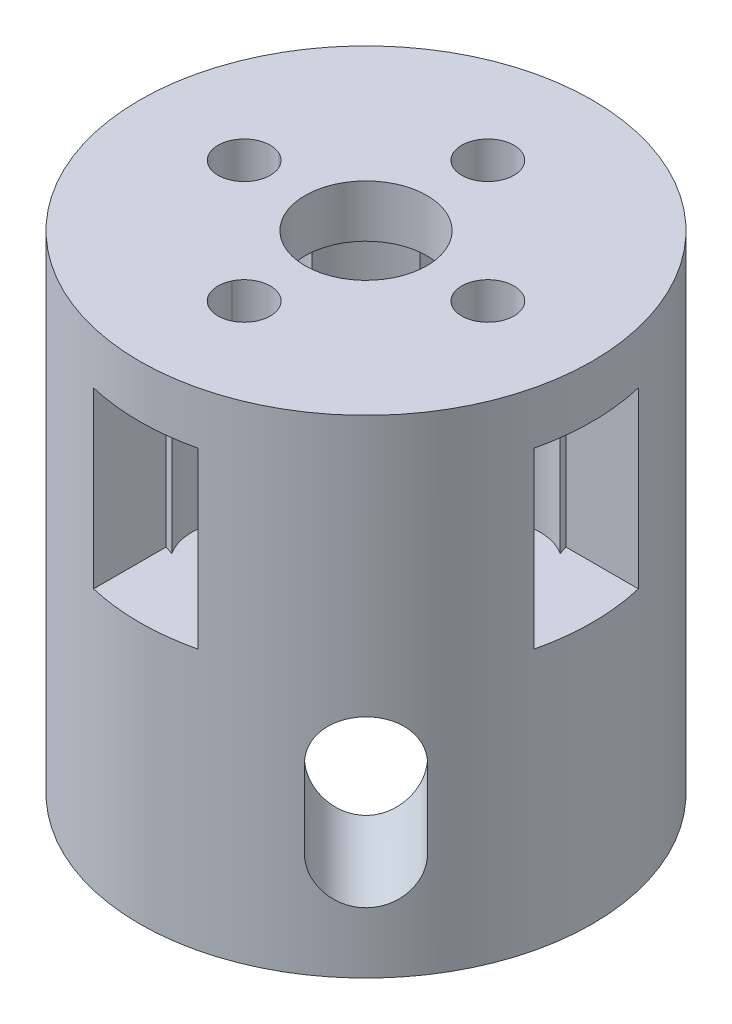
SolidWorks part; units mm, degrees
note: The reader was unsure of these and kept them because the rebuilt part matched: shared geometry of "Sketch1<4>", "Sketch1<7>", "Sketch1<6>".
ref_plane "Front Plane" through (0, 0, 0) normal (0, 0, 1) x (1, 0, 0)
ref_plane "Top Plane" through (0, 0, 0) normal (0, 1, 0) x (1, 0, 0)
ref_plane "Right Plane" through (0, 0, 0) normal (1, 0, 0) x (0, 0, -1)
sketch "Sketch1" plane through (0, 0, 0) normal (0, 1, 0) x (1, 0, 0)
  line L0 (-7, 0) -> (7, 0) construction
  circle A0 centre (0, 0) radius 13
  circle A1 centre (0, 0) radius 6.5
  circle A2 centre (0, 0) radius 9
  circle A3 centre (-7, 0) radius 1.5
  circle A4 centre (7, 0) radius 1.5
  circle A5 centre (0, 7) radius 1.5
  circle A6 centre (0, -7) radius 1.5
  circle A7 centre (7, 0) radius 3
  circle A8 centre (0, -7) radius 3
  circle A9 centre (-7, 0) radius 3
  circle A10 centre (0, 7) radius 3
  circle A11 centre (0, 0) radius 3.5
  point P16 (0, 0)
  point P24 (0, 0)
  dimension "D1" = 26
  dimension "D2" = 13
  dimension "D3" = 18
  dimension "D4" = 3
  dimension "D5" = 3
  dimension "D9" = 6
  dimension "D11" = 7
  dimension "D6" = 14
  dimension "D8" = 7
  dimension "D7" = 2
  dimension "D10" = 4
extrude "Boss-Extrude2" add sketch "Sketch1" against normal blind 25 contours A9 A2 A8 A1 | A8 A2 A7 A1 | A10 A1 A7 A2 | A10 A2 A9 A1
extrude "Boss-Extrude3" add sketch "Sketch1<4>" along normal blind 3
sketch "Sketch1<4>" plane through (0, 0, 0) normal (0, 1, 0) x (1, 0, 0) same geometry as "Sketch1"
extrude "Cut-Extrude2" cut sketch "Sketch1<7>" along normal up to surface (3 mm away) contours A1 A5
sketch "Sketch1<7>" plane through (0, 0, 0) normal (0, 1, 0) x (1, 0, 0) same geometry as "Sketch1"
extrude "Boss-Extrude4" add sketch "Sketch1<6>" against normal blind 15 from offset 10 offset against normal yes
sketch "Sketch1<6>" plane through (0, 0, 0) normal (0, 1, 0) x (1, 0, 0) same geometry as "Sketch1"
ref_plane "Plane1" through (6.364, 0, 6.364) normal (0.7071, 0, 0.7071) x (0.7071, 0, -0.7071)
sketch "Sketch3" plane through (0, 0, 0) normal (0, -1, 0) x (1, 0, 0)
  line L0 (-3, 12.6491) -> (-3, -12.6491)
  line L1 (3, 12.6491) -> (3, -12.6491)
  line L2 (-12.6491, -3) -> (12.6491, -3)
  line L3 (12.6491, 3) -> (-12.6491, 3)
  circle A0 centre (0, 0) radius 13
  circle A1 centre (0, 0) radius 9
  arc M10 (8.6429, -2.5102) -> (2.5102, -8.6429) centre (0, 0) cw
  circle M15 centre (0, 0) radius 13
  arc M19 (2.5102, 8.6429) -> (8.6429, 2.5102) centre (0, 0) cw
  arc M23 (-2.5102, -8.6429) -> (-8.6429, -2.5102) centre (0, 0) cw
  dimension "D1" = 26
  dimension "D6" = 18
  dimension "D2" = 6
  dimension "D3" = 3
  dimension "D4" = 6
  dimension "D5" = 3
extrude "Boss-Extrude6" add sketch "Sketch3" along normal up to surface (25 mm away) contours L2 L0 M15 M23 | L2 L1 M10 M15 | L3 L1 M15 M19 | A1 L0 L3 M15 up to face at (0.1706, -25, -0.1706)
sketch "Sketch4" plane through (0, -25, 0) normal (0, -1, 0) x (1, 0, 0)
  circle A0 centre (0, 0) radius 9
  circle A1 centre (0, 0) radius 13
  arc M1 (-8.4853, 3) -> (-8.4853, -3) centre (0, 0) ccw
  line M2 (-8.4853, -3) -> (-12.6491, -3)
  line M4 (-3, -12.6491) -> (-3, -8.4853)
  arc M5 (-3, -8.4853) -> (3, -8.4853) centre (0, 0) ccw
  line M6 (3, -8.4853) -> (3, -12.6491)
  line M8 (12.6491, -3) -> (8.4853, -3)
  arc M9 (8.4853, -3) -> (8.4853, 3) centre (0, 0) ccw
  line M10 (8.4853, 3) -> (12.6491, 3)
  line M12 (3, 12.6491) -> (3, 8.4853)
  arc M13 (3, 8.4853) -> (-3, 8.4853) centre (0, 0) ccw
  line M14 (-3, 8.4853) -> (-3, 12.6491)
  line M16 (-12.6491, 3) -> (-8.4853, 3)
extrude "Boss-Extrude7" add sketch "Sketch4" against normal blind 15 contours A1 M4 M6 M5 | A1 M16 M2 M1 | A1 M8 M10 M9 | A1 M12 M14 M13
sketch "Sketch2" plane through (20.0208, 0, -7.2929) normal (-0.7071, 0, -0.7071) x (-0.7071, 0, 0.7071)
  line L0 (19.3137, -14.5) -> (19.3137, 0) construction
  line L1 (10.3137, -25) -> (27.2001, -25) construction
  line L2 (19.3137, -16.5) -> (19.3137, -19) construction
  line L3 (16.8137, -14.5) -> (16.8137, -19)
  line L4 (21.8137, -14.5) -> (21.8137, -19)
  arc A0 (21.8137, -14.5) -> (16.8137, -14.5) centre (19.3137, -14.5) ccw
  arc A1 (16.8137, -19) -> (21.8137, -19) centre (19.3137, -19) ccw
  dimension "D1" = 5
  dimension "D3" = 5
  dimension "D5" = 4.5
  dimension "D2" = 14.5
  dimension "D4" = 6
extrude "Cut-Extrude1" cut sketch "Sketch2" against normal through all both and the other way through all
